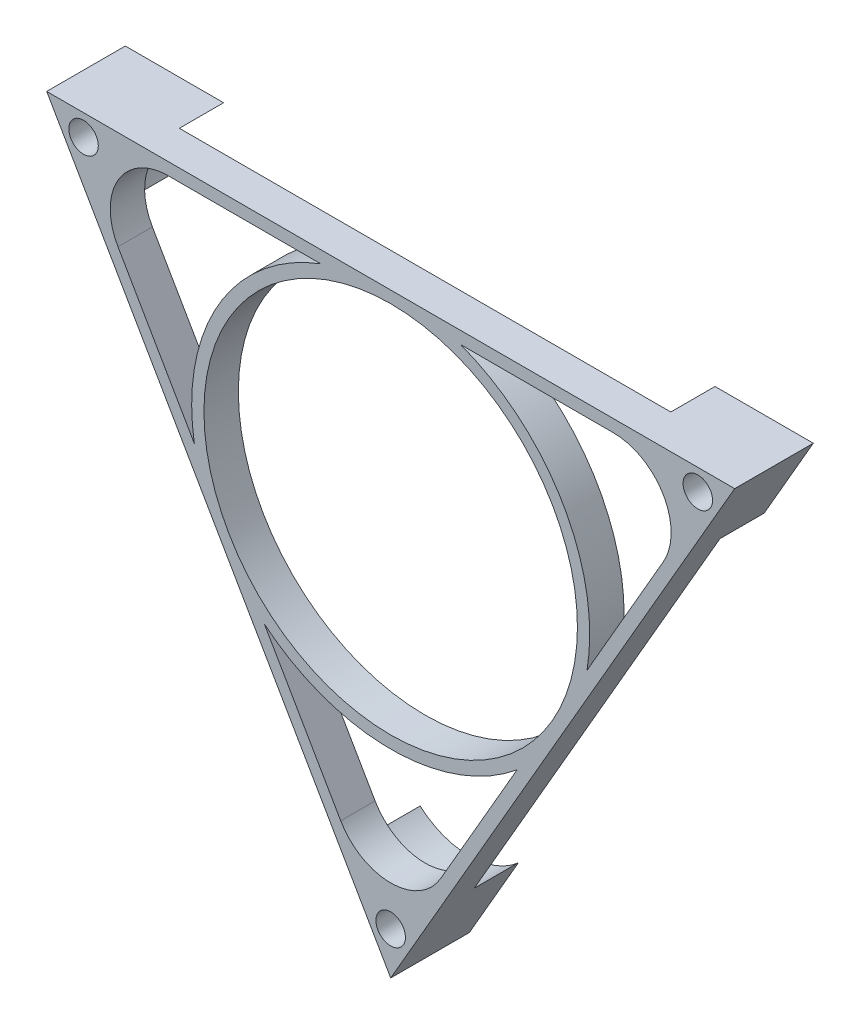
SolidWorks part; units mm, degrees
material "ABS"
ref_plane "Front Plane" through (0, 0, 0) normal (0, 0, 1) x (1, 0, 0)
ref_plane "Top Plane" through (0, 0, 0) normal (0, 1, 0) x (1, 0, 0)
ref_plane "Right Plane" through (0, 0, 0) normal (1, 0, 0) x (0, 0, -1)
sketch "Sketch1" plane through (0, 0, 0) normal (0, 0, 1) x (1, 0, 0)
  line L5 (0, -80.829) -> (70, 40.4145)
  line L6 (70, 40.4145) -> (-70, 40.4145)
  line L7 (-70, 40.4145) -> (0, -80.829)
  circle A0 centre (0, 0) radius 38
  circle A1 centre (0, 0) radius 40.4145 construction
  circle A3 centre (0, 0) radius 38
  circle A5 centre (0, 0) radius 38
  circle A7 centre (0, 0) radius 38
  point P21 (0, 0)
  dimension "D1" = 76
  dimension "D6" = 140
  dimension "D5" = 4
extrude "Boss-Extrude1" add sketch "Sketch1" along normal blind 2 contours L6 L7 L5 A0 region at (-33.3961, -19.2812, 0)
sketch "Sketch2" plane through (0, 0, 0) normal (0, 0, 1) x (1, 0, 0)
  line L6 (70, 40.4145) -> (-70, 40.4145)
  line L7 (-70, 40.4145) -> (0, -80.829)
  line L8 (0, -80.829) -> (70, 40.4145)
  line L9 (-50, 40.4145) -> (-70, 40.4145)
  line L10 (-70, 40.4145) -> (-60, 23.094)
  arc A0 (-60, 23.094) -> (-50, 40.4145) centre (-45.3175, 26.1641) cw
  dimension "D4" = 15
  dimension "D2" = 20
  dimension "D3" = 20
  dimension "D1" = 0
extrude "Boss-Extrude2" add sketch "Sketch2" against normal blind 14
pattern_circular "CirPattern1" count 3 over 360 about axis through (0, 0, 2) along (0, 0, -1) of "Boss-Extrude2"
sketch "Sketch5" plane through (0, 0, 0) normal (0, 0, -1) x (-1, 0, 0)
  line L0 (-10, -63.5085) -> (-60, 23.094) construction
  line L1 (-50, 40.4145) -> (50, 40.4145) construction
  line L2 (-39.9543, -6.6262) -> (-31.5612, -21.1634) construction
  line L3 (-55.4937, 20.2889) -> (-39.9543, -6.6262)
  line L4 (-45.3175, 37.9145) -> (-14.2387, 37.9145)
  circle A1 centre (0, 0) radius 38 construction
  arc A3 (-55.4937, 20.2889) -> (-45.3175, 37.9145) centre (-45.3175, 26.1641) cw
  arc A4 (-14.2387, 37.9145) -> (-39.9543, -6.6262) centre (0, 0) ccw
  dimension "D2" = 2.5
  dimension "D1" = 2.5
extrude "Cut-Extrude1" cut sketch "Sketch5" against normal through all both and the other way through all
pattern_circular "CirPattern3" count 3 over 360 about axis through (0, 0, 2) along (0, 0, 1) of "Cut-Extrude1"
sketch "Sketch8" plane through (0, 0, 0) normal (0, 0, -1) x (-1, 0, 0)
  line L0 (-39.9543, -6.6262) -> (-55.4937, 20.2889) construction
  line L1 (-45.3175, 37.9145) -> (-14.2387, 37.9145) construction
  line L2 (14.2387, 37.9145) -> (45.3175, 37.9145) construction
  line L3 (-60, 23.094) -> (-10, -63.5085)
  line L4 (10, -63.5085) -> (60, 23.094)
  line L5 (50, 40.4145) -> (-50, 40.4145)
  line L6 (-60, 23.094) -> (-10, -63.5085)
  line L7 (10, -63.5085) -> (60, 23.094)
  line L8 (50, 40.4145) -> (-50, 40.4145)
  line L9 (55.4937, 20.2889) -> (39.9543, -6.6262) construction
  line L10 (-39.9543, -6.6262) -> (-55.4937, 20.2889)
  line L11 (-45.3175, 37.9145) -> (-14.2387, 37.9145)
  line L12 (14.2387, 37.9145) -> (45.3175, 37.9145)
  line L13 (55.4937, 20.2889) -> (39.9543, -6.6262)
  line L14 (-10.1762, -58.2034) -> (-25.7156, -31.2883) construction
  line L15 (25.7156, -31.2883) -> (10.1762, -58.2034) construction
  line L16 (25.7156, -31.2883) -> (10.1762, -58.2034)
  line L17 (-10.1762, -58.2034) -> (-25.7156, -31.2883)
  arc A0 (-45.3175, 37.9145) -> (-55.4937, 20.2889) centre (-45.3175, 26.1641) ccw construction
  arc A1 (-14.2387, 37.9145) -> (-39.9543, -6.6262) centre (0, 0) ccw construction
  circle A2 centre (0, 0) radius 38 construction
  arc A3 (-10, -63.5085) -> (10, -63.5085) centre (0, -52.3282) ccw
  arc A4 (60, 23.094) -> (50, 40.4145) centre (45.3175, 26.1641) ccw
  arc A5 (-50, 40.4145) -> (-60, 23.094) centre (-45.3175, 26.1641) ccw
  arc A6 (-10, -63.5085) -> (10, -63.5085) centre (0, -52.3282) ccw
  arc A7 (60, 23.094) -> (50, 40.4145) centre (45.3175, 26.1641) ccw
  arc A8 (-50, 40.4145) -> (-60, 23.094) centre (-45.3175, 26.1641) ccw
  arc A9 (39.9543, -6.6262) -> (14.2387, 37.9145) centre (0, 0) ccw construction
  arc A10 (55.4937, 20.2889) -> (45.3175, 37.9145) centre (45.3175, 26.1641) ccw construction
  arc A11 (-45.3175, 37.9145) -> (-55.4937, 20.2889) centre (-45.3175, 26.1641) ccw
  arc A12 (-14.2387, 37.9145) -> (-39.9543, -6.6262) centre (0, 0) ccw
  circle A13 centre (0, 0) radius 38
  arc A14 (39.9543, -6.6262) -> (14.2387, 37.9145) centre (0, 0) ccw
  arc A15 (55.4937, 20.2889) -> (45.3175, 37.9145) centre (45.3175, 26.1641) ccw
  arc A16 (-25.7156, -31.2883) -> (25.7156, -31.2883) centre (0, 0) ccw construction
  arc A17 (-10.1762, -58.2034) -> (10.1762, -58.2034) centre (0, -52.3282) ccw construction
  arc A18 (-10.1762, -58.2034) -> (10.1762, -58.2034) centre (0, -52.3282) ccw
  arc A19 (-25.7156, -31.2883) -> (25.7156, -31.2883) centre (0, 0) ccw
  dimension "D1" = 0
extrude "Boss-Extrude5" add sketch "Sketch8" along normal blind 5
sketch "Sketch6" plane through (0, 0, 2) normal (0, 0, 1) x (1, 0, 0)
  line L1 (62.5, 36.0844) -> (-62.5, 36.0844) construction
  line L2 (-62.5, 36.0844) -> (0, -72.1688) construction
  line L3 (0, -72.1688) -> (62.5, 36.0844) construction
  circle A0 centre (-62.5, 36.0844) radius 1.65
  circle A1 centre (62.5, 36.0844) radius 1.65
  circle A2 centre (0, -72.1688) radius 1.65
  circle A3 centre (0, 0) radius 36.0844 construction
  dimension "D1" = 3.3
  dimension "D2" = 3.3
  dimension "D3" = 3.3
  dimension "D4" = 125
extrude "Cut-Extrude2" cut sketch "Sketch6" against normal through all
sketch "Sketch10" plane through (0, 0, 2) normal (0, 0, 1) x (1, 0, 0)
  line L0 (32.2987, 40.4145) -> (75.0594, 47.9544)
  line L1 (70, 40.4145) -> (-70, 40.4145) construction
  line L2 (75.0594, 47.9544) -> (79.0594, 41.0262)
  line L3 (79.0594, 41.0262) -> (51.1494, 7.7642)
  line L4 (0, -80.829) -> (70, 40.4145) construction
  line L5 (0, 0) -> (109.5672, 63.2586) construction
  line L6 (51.1494, 7.7642) -> (70, 40.4145)
  line L7 (70, 40.4145) -> (32.2987, 40.4145)
  point P10 (77.0594, 44.4903)
  dimension "D1" = 10
  dimension "D2" = 10
  dimension "D3" = 8
extrude "Boss-Extrude6" [suppressed] add sketch "Sketch10" against normal up to surface (6 mm away) from offset 10 offset against normal yes
fillet "Fillet1" [suppressed] radius 5
sketch "Sketch11" plane through (0, 0, 2) normal (0, 0, 1) x (1, 0, 0)
  circle A0 centre (-62.5, 36.0844) radius 3
  circle A1 centre (62.5, 36.0844) radius 3
  circle A2 centre (0, -72.1688) radius 3
  point P10 (0, 0)
  dimension "D1" = 6
  dimension "D2" = 3
extrude "Cut-Extrude3" cut sketch "Sketch11" against normal offset from surface (13 mm away) 3 up to face at (1.65, -72.1688, -14)
chamfer "Chamfer1" distance 2.2 angle 45 3 edges at (-1.65, -72.1688, -11) (60.85, 36.0844, -11) (-64.15, 36.0844, -11)
